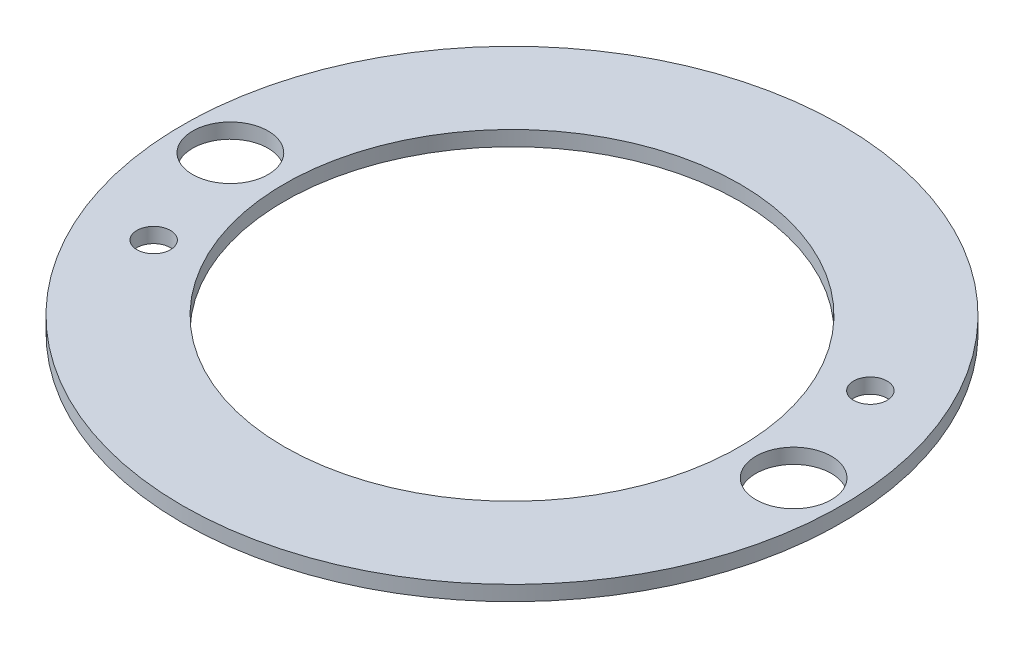
SolidWorks part; units mm, degrees
ref_plane "Front Plane" through (0, 0, 0) normal (0, 0, 1) x (1, 0, 0)
ref_plane "Top Plane" through (0, 0, 0) normal (0, 1, 0) x (1, 0, 0)
ref_plane "Right Plane" through (0, 0, 0) normal (1, 0, 0) x (0, 0, -1)
sketch "Sketch1" plane through (0, 0, 0) normal (0, 1, 0) x (1, 0, 0)
  circle A0 centre (0, 0) radius 69.85
extrude "Boss-Extrude1" add sketch "Sketch1" along normal blind 3.175
sketch "Sketch2" plane through (0, 3.175, 0) normal (0, 1, 0) x (1, 0, 0)
  line L0 (59.69, 0) -> (-59.69, 0) construction
  line L1 (51.7955, 24.1526) -> (-51.7955, -24.1526) construction
  circle A0 centre (-59.69, 0) radius 8.001
  circle A1 centre (59.69, 0) radius 8.001
  circle A2 centre (-51.7955, -24.1526) radius 3.556
  circle A3 centre (51.7955, 24.1526) radius 3.556
  point P4 (0, 0)
  point P9 (0, 0)
extrude "Cut-Extrude1" cut sketch "Sketch2" against normal blind 3.175
sketch "Sketch3" plane through (0, 3.175, 0) normal (0, 1, 0) x (1, 0, 0)
  circle A0 centre (0, 0) radius 48.26
extrude "Cut-Extrude2" cut sketch "Sketch3" against normal blind 3.175
